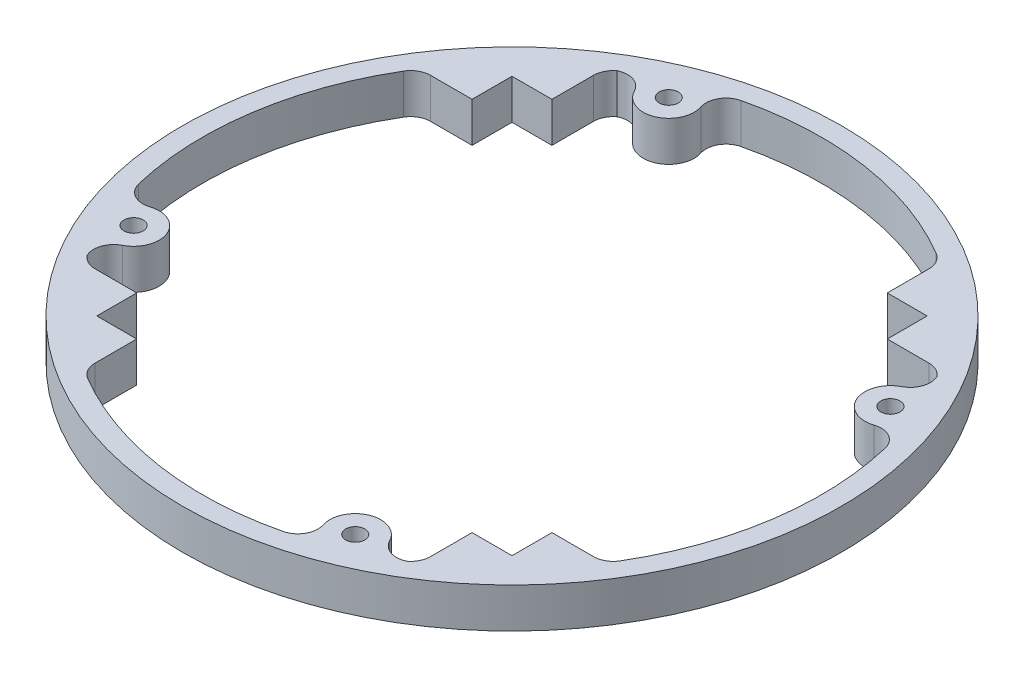
SolidWorks part; units mm, degrees
note: '?' marks a value the reader was unsure of.
material "6061-T6 (SS)"
ref_plane "Front Plane" through (0, 0, 0) normal (0, 0, 1) x (1, 0, 0)
ref_plane "Top Plane" through (0, 0, 0) normal (0, 1, 0) x (1, 0, 0)
ref_plane "Right Plane" through (0, 0, 0) normal (1, 0, 0) x (0, 0, -1)
sketch "Sketch1" plane through (0, 0, 0) normal (0, 1, 0) x (1, 0, 0)
  line L0 (0, 0) -> (0, 84.2831) construction
  line L1 (-52, 52) -> (52, 52) construction
  line L2 (-52, 52) -> (-52, -52) construction
  line L3 (-52, -52) -> (52, -52) construction
  line L4 (52, 52) -> (52, -52) construction
  line L5 (0, 0) -> (-99.9306, 0) construction
  line L6 (0, 0) -> (-52, 52) construction
  line L7 (0, 0) -> (-31.8699, 76.9407) construction
  line L8 (-42, 52) -> (-52, 52)
  line L9 (-52, 52) -> (-52, 42)
  line L10 (-52, 42) -> (-65.192, 42)
  line L11 (-42, 52) -> (-42, 65.192)
  line L12 (-35.4887, 68.9533) -> (-33.6765, 64.5783)
  line L13 (-23.663, 73.8516) -> (-21.8509, 69.4766)
  line L14 (42, 52) -> (42, 65.192)
  line L15 (52, 52) -> (42, 52)
  line L16 (52, 42) -> (52, 52)
  line L17 (52, 42) -> (65.192, 42)
  line L18 (68.9533, 35.4887) -> (64.5783, 33.6765)
  line L19 (73.8516, 23.663) -> (69.4766, 21.8509)
  line L20 (52, -42) -> (65.192, -42)
  line L21 (52, -52) -> (52, -42)
  line L22 (42, -52) -> (52, -52)
  line L23 (42, -52) -> (42, -65.192)
  line L24 (35.4887, -68.9533) -> (33.6765, -64.5783)
  line L25 (23.663, -73.8516) -> (21.8509, -69.4766)
  line L26 (-42, -52) -> (-42, -65.192)
  line L27 (-52, -52) -> (-42, -52)
  line L28 (-52, -42) -> (-52, -52)
  line L29 (-52, -42) -> (-65.192, -42)
  line L30 (-68.9533, -35.4887) -> (-64.5783, -33.6765)
  line L31 (-73.8516, -23.663) -> (-69.4766, -21.8509)
  circle A0 centre (0, 0) radius 82.55
  arc A1 (-65.192, 42) -> (-77.55, 0) centre (0, 0) ccw
  arc A2 (-42, 65.192) -> (-35.4887, 68.9533) centre (0, 0) cw
  arc A3 (-33.6765, 64.5783) -> (-21.8509, 69.4766) centre (-27.7637, 67.0275) ccw
  arc A4 (0, 77.55) -> (-23.663, 73.8516) centre (0, 0) ccw
  arc A5 (42, 65.192) -> (0, 77.55) centre (0, 0) ccw
  arc A6 (65.192, 42) -> (68.9533, 35.4887) centre (0, 0) cw
  arc A7 (64.5783, 33.6765) -> (69.4766, 21.8509) centre (67.0275, 27.7637) ccw
  arc A8 (77.55, 0) -> (73.8516, 23.663) centre (0, 0) ccw
  arc A9 (65.192, -42) -> (77.55, 0) centre (0, 0) ccw
  arc A10 (42, -65.192) -> (35.4887, -68.9533) centre (0, 0) cw
  arc A11 (33.6765, -64.5783) -> (21.8509, -69.4766) centre (27.7637, -67.0275) ccw
  arc A12 (0, -77.55) -> (23.663, -73.8516) centre (0, 0) ccw
  arc A13 (-42, -65.192) -> (0, -77.55) centre (0, 0) ccw
  arc A14 (-65.192, -42) -> (-68.9533, -35.4887) centre (0, 0) cw
  arc A15 (-64.5783, -33.6765) -> (-69.4766, -21.8509) centre (-67.0275, -27.7637) ccw
  arc A16 (-77.55, 0) -> (-73.8516, -23.663) centre (0, 0) ccw
  point P21 (-22.7569, 71.6641)
  point P61 (0, 0)
  dimension "D1" = 165.1
  dimension "D2" = 104
  dimension "D3" = 22.5
  dimension "D4" = 5
  dimension "D5" = 72.55
  dimension "D6" = 12.8
  dimension "D7" = 10
  dimension "D8" = 4
extrude "Boss-Extrude1" add sketch "Sketch1" along normal blind 10
fillet "Fillet1" radius 5 16 edges at (-73.8516, 5, 23.663) (-68.9533, 5, 35.4887) (-42, 5, 65.192) (-65.192, 5, 42) (23.663, 5, 73.8516) (35.4887, 5, 68.9533) (42, 5, 65.192) (65.192, 5, 42) (73.8516, 5, -23.663) (68.9533, 5, -35.4887) (65.192, 5, -42) (42, 5, -65.192) (-35.4887, 5, -68.9533) (-23.663, 5, -73.8516) (-42, 5, -65.192) (-65.192, 5, -42)
hole_wizard "#12 (0.189) Diameter Hole1" positions "Sketch4" profile "Sketch3" hole size "#12" standard "ANSI Inch" end condition through all
sketch "Sketch4" plane through (0, 10, 0) normal (0, 1, 0) x (1, 0, 0)
  point P0 (67.0275, 27.7637)
sketch "Sketch3" plane through (67.0275, 10, -27.7637) normal (1, 0, 0) x (0, 0, 1)
  line L0 (0, 0) -> (0, 10)
  line L1 (0, 10) -> (2.4003, 10)
  line L2 (2.4003, 10) -> (2.4003, 0)
  line L5 (2.4003, 0) -> (0, 0)
  line L11 (0, -6.35) -> (0, 107.95) construction
  dimension "Thru Hole Dia." = 4.8006
  dimension "Thru Hole Depth" = 10
hole_wizard "#10-24 Tapped Hole1" [suppressed] positions "Sketch8" profile "Sketch9" tap size "#10-24" standard "ANSI Inch"
sketch "Sketch8" plane through (0, 0, -52) normal (0, 0, 1) x (1, 0, 0)
  line L0 (52, 0) -> (42, 10)
  point P0 (47, 5)
  point P10 (47, 5)
sketch "Sketch9" plane through (47, 5, -52) normal (1, 0, 0) x (0, -1, 0)
  line L0 (0, 0) -> (0, 30.55)
  line L1 (0, 30.55) -> (1.8986, 30.55)
  line L2 (1.8986, 30.55) -> (1.8986, 0)
  line L5 (1.8986, 0) -> (0, 0)
  line L11 (0, -6.35) -> (0, 107.95) construction
  dimension "Thru Tap Drill Dia." = 3.7973
  dimension "Thru Tap Drill Depth" = 30.55
cosmetic thread "Hole Thread2" [suppressed] parameters "D2"=4.826
ref_axis "Axis1" through (0, 10.5, 0) along (0, -1, 0)?
pattern_circular "CirPattern1" count 4 over 360 about axis through (0, 0, 0) along (0, 1, 0) of "#12 (0.189) Diameter Hole1", "#10-24 Tapped Hole1"
equation "\"TubeDiameter\" = 6.500in"
equation "\"D1@Sketch1\"=\"TubeDiameter\""
equation "\"D5@Sketch1\"=\"TubeDiameter\"/2-10mm"
